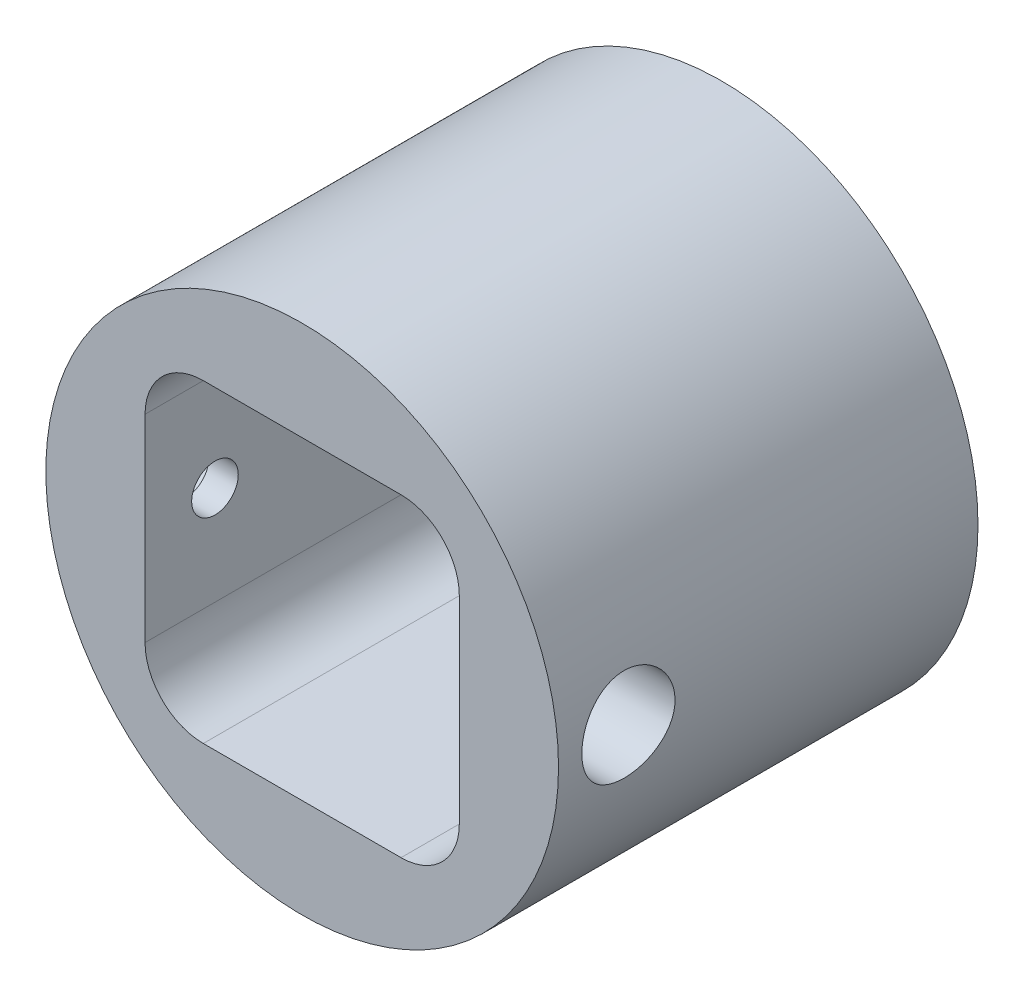
SolidWorks part; units mm, degrees
material "ABS PC"
ref_plane "Front Plane" through (0, 0, 0) normal (0, 0, 1) x (1, 0, 0)
ref_plane "Top Plane" through (0, 0, 0) normal (0, 1, 0) x (1, 0, 0)
ref_plane "Right Plane" through (0, 0, 0) normal (1, 0, 0) x (0, 0, -1)
sketch "Sketch1" plane through (0, 0, 0) normal (0, 0, 1) x (1, 0, 0)
  circle A1 centre (-4.2426, 4.2426) radius 1.5
  circle A5 centre (0, 0) radius 11
  circle A6 centre (4.2426, 4.2426) radius 1.5
  circle A7 centre (4.2426, -4.2426) radius 1.5
  circle A8 centre (-4.2426, -4.2426) radius 1.5
  point P14 (0, 0)
  dimension "D2" = 3
  dimension "D3" = 22
  dimension "D1" = 4
extrude "Boss-Extrude1" add sketch "Sketch1" along normal blind 18
sketch "Sketch2" plane through (0, 0, 18) normal (0, 0, 1) x (1, 0, 0)
  line L0 (-4.2426, 6.7426) -> (4.2426, 6.7426)
  line L1 (-6.7426, 4.2426) -> (-6.7426, -4.2426)
  line L2 (-4.2426, -6.7426) -> (4.2426, -6.7426)
  line L3 (6.7426, 4.2426) -> (6.7426, -4.2426)
  circle A0 centre (-4.2426, 4.2426) radius 2.5
  circle A4 centre (4.2426, 4.2426) radius 2.5
  circle A5 centre (4.2426, -4.2426) radius 2.5
  circle A6 centre (-4.2426, -4.2426) radius 2.5
  point P15 (0, 0)
  circle M6 centre (-4.2426, 4.2426) radius 1.5
  circle M14 centre (4.2426, -4.2426) radius 1.5
  circle M15 centre (4.2426, 4.2426) radius 1.5
  circle M16 centre (-4.2426, -4.2426) radius 1.5
  dimension "D1" = 5
  dimension "D2" = 4
sketch "Sketch3" plane through (0, 0, 0) normal (1, 0, 0) x (0, 0, -1)
  line L0 (-18, 11) -> (-18, -11) construction
  circle A0 centre (-15, 0) radius 1
  dimension "D1" = 2
  dimension "D2" = 3
extrude "Cut-Extrude2" cut sketch "Sketch3" against normal through all both and the other way through all
sketch "Sketch4" plane through (0, 0, 0) normal (1, 0, 0) x (0, 0, -1)
  circle A0 centre (-15, 0) radius 2
  dimension "D1" = 4
extrude "Cut-Extrude3" cut sketch "Sketch4" against normal blind 5 from offset 8 offset against normal yes
extrude "Cut-Extrude4" cut sketch "Sketch4<2>" along normal blind 5 from offset 8
sketch "Sketch4<2>" plane through (0, 0, 0) normal (1, 0, 0) x (0, 0, -1) same geometry as "Sketch4"
extrude "Cut-Extrude5" cut sketch "Sketch2" against normal blind 16 contours A6 L2 A5 L3 A4 L0 A0 L1 | A4 M15 | A0 M6 | M6 | M16 | A6 M16 | M14 | A5 M14 | M15 region at (0, 0, 18) region at (-2.5249, 5.9604, 18) region at (5.9604, 5.9604, 18) region at (-4.2426, -1.8134, 18) region at (5.9604, -5.9604, 18) region at (-4.2426, 4.2426, 18) region at (4.2426, -4.2426, 18) region at (4.2426, 4.2426, 18) region at (-4.2426, -4.2426, 18)
